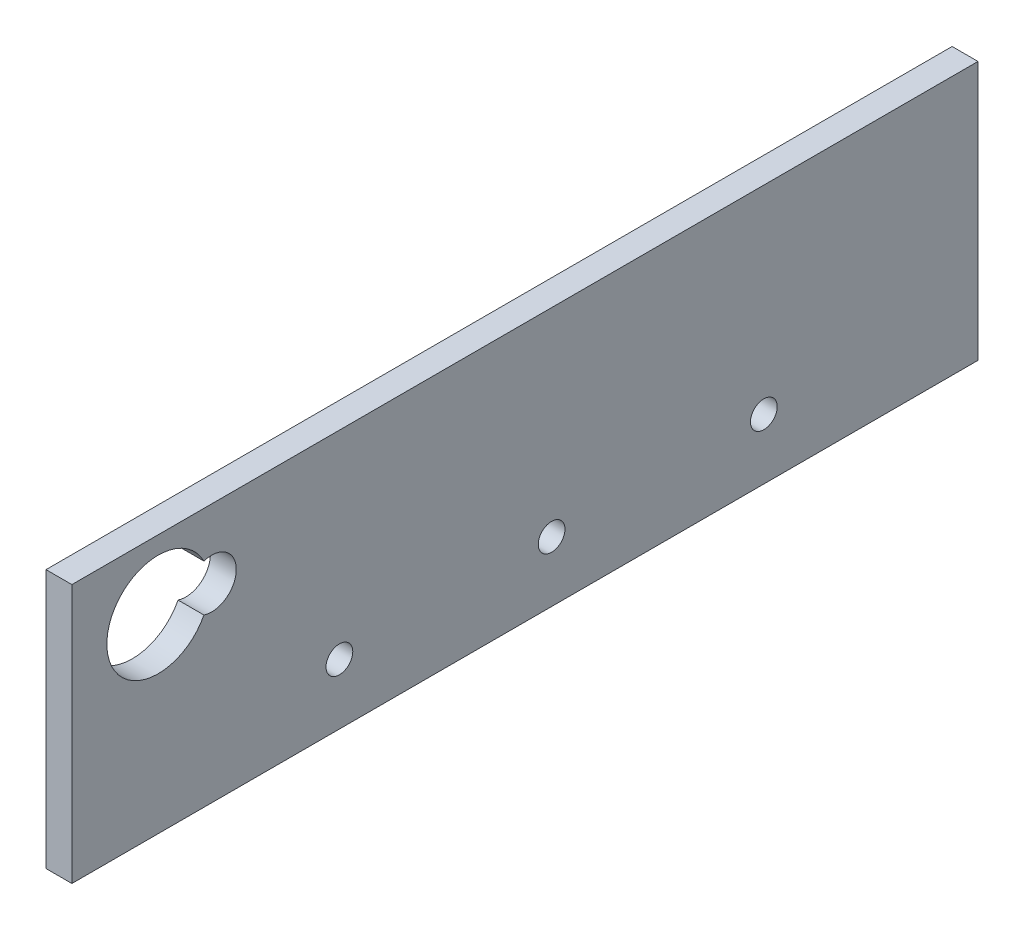
SolidWorks part; units mm, degrees
ref_plane "Ebene vorne" through (0, 0, 0) normal (0, 0, 1) x (1, 0, 0)
ref_plane "Ebene oben" through (0, 0, 0) normal (0, 1, 0) x (1, 0, 0)
ref_plane "Ebene rechts" through (0, 0, 0) normal (1, 0, 0) x (0, 0, -1)
sketch "Skizze1" plane through (0, 0, 0) normal (1, 0, 0) x (0, 0, -1)
  line L1 (0, 0) -> (105, 0)
  line L2 (0, 0) -> (0, 30)
  line L3 (0, 30) -> (105, 30)
  line L4 (105, 0) -> (105, 30)
  dimension "D1" = 105
  dimension "D2" = 30
extrude "Aufsatz-Linear austragen1" add sketch "Skizze1" along normal blind 3
sketch "Skizze2" plane through (3, 0, 0) normal (1, 0, 0) x (0, 0, -1)
  line L0 (10, 0) -> (10, 22) construction
  line L1 (0, 0) -> (105, 0) construction
  line L2 (31, 0) -> (31, 7) construction
  line L3 (55.5919, 0) -> (55.5919, 7) construction
  line L4 (80.1837, 0) -> (80.1837, 7) construction
  line L5 (80.1837, 7) -> (55.5919, 7) construction
  line L6 (55.5919, 7) -> (31, 7) construction
  line L7 (0, 30) -> (0, 0) construction
  circle A0 centre (10, 22) radius 1.55
  circle A1 centre (31, 7) radius 1.55
  circle A2 centre (55.5919, 7) radius 1.55
  circle A3 centre (80.1837, 7) radius 1.55
  dimension "D6" = 3.1
  dimension "D1" = 21
  dimension "D3" = 15
  dimension "D4" = 7
  dimension "D5" = 10
  dimension "D7" = 49.1837
extrude "Bohrungen" cut sketch "Skizze2" against normal through all
sketch "Skizze6" plane through (0, 0, 0) normal (-1, 0, 0) x (0, 0, 1)
  line L0 (-10, 22) -> (0, 22) construction
  line L1 (0, -1.65) -> (0, 1.65) construction
  line L2 (-10, 22) -> (-16.2, 22) construction
  arc A0 (-15.3, 19.2958) -> (-15.3, 24.7042) centre (-10, 22) ccw
  arc A1 (-15.3, 24.7042) -> (-15.3, 19.2958) centre (-16.2, 22) ccw
  dimension "D1" = 11.9
  dimension "D2" = 5.7
  dimension "D3" = 6.2
extrude "Schnitt-Linear austragen3" cut sketch "Skizze6" against normal up to surface (3 mm away) up to face at (3, 22, -11.55)
